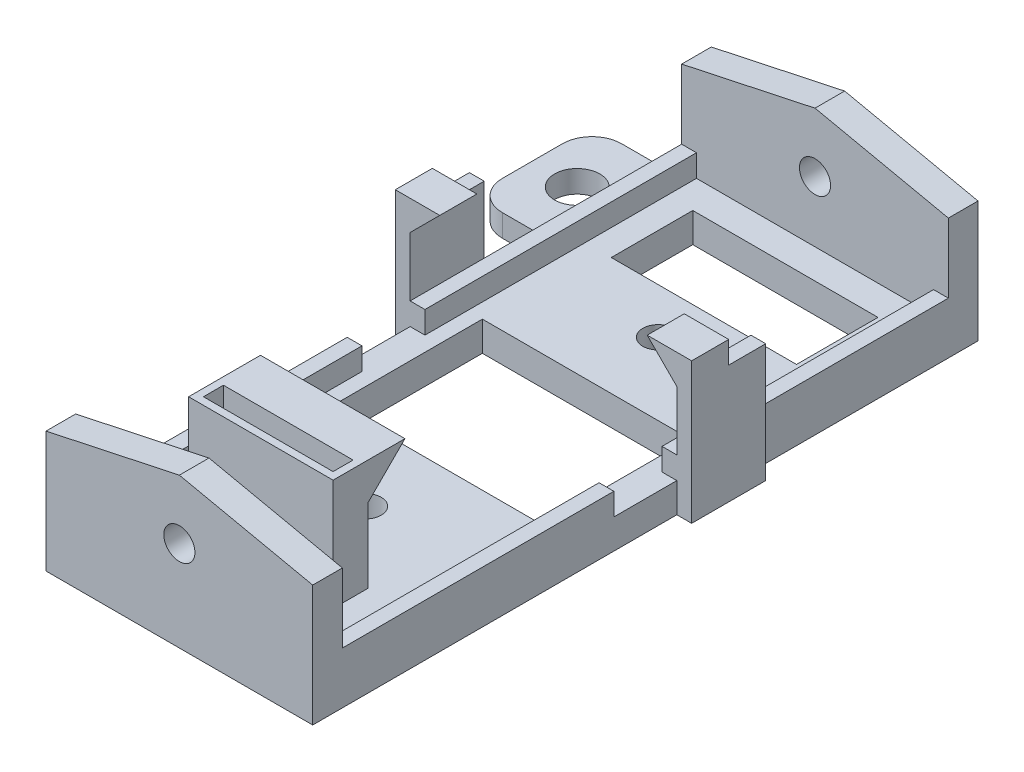
SolidWorks part; units mm, degrees
ref_plane "Front Plane" through (0, 0, 0) normal (0, 0, 1) x (1, 0, 0)
ref_plane "Top Plane" through (0, 0, 0) normal (0, 1, 0) x (1, 0, 0)
ref_plane "Right Plane" through (0, 0, 0) normal (1, 0, 0) x (0, 0, -1)
sketch "Sketch1" plane through (0, 0, 0) normal (0, 0, 1) x (1, 0, 0)
  line L2 (-40.4, 110) -> (0, 118.6383) construction
  line L3 (-18, 114.7896) -> (0, 114.7896)
  line L4 (0, 114.7896) -> (18, 114.7896)
  line L5 (0, 118.6383) -> (40.4, 110) construction
  line L11 (18, 114.7896) -> (18, 121.7896)
  line L12 (18, 121.7896) -> (16, 121.7896)
  line L13 (16, 121.7896) -> (16, 118.7896)
  line L14 (16, 118.7896) -> (-16, 118.7896)
  line L15 (-16, 118.7896) -> (-16, 121.7896)
  line L16 (-16, 121.7896) -> (-18, 121.7896)
  line L17 (-18, 121.7896) -> (-18, 114.7896)
  point P15 (0, 118.7896)
  dimension "D1" = 32
  dimension "D2" = 2
  dimension "D3" = 3
  dimension "D4" = 4
extrude "Boss-Extrude1" add sketch "Sketch1" along normal up to surface (89.8 mm away)
sketch "Sketch2" plane through (0, 114.7896, 0) normal (0, -1, 0) x (1, 0, 0)
  line L0 (18, 89.8) -> (18, 0) construction
  line L5 (-14, 54.9) -> (14, 54.9)
  line L6 (-14, 54.9) -> (-14, 34.9)
  line L7 (-14, 34.9) -> (14, 34.9)
  line L8 (14, 54.9) -> (14, 34.9)
  point P4 (0, 34.9)
  point P8 (18, 44.9)
  point P9 (14, 44.9)
  dimension "D1" = 4
  dimension "D2" = 20
extrude "Cut-Extrude1" cut sketch "Sketch2" against normal up to next
sketch "Sketch3" plane through (-18, 0, 0) normal (-1, 0, 0) x (0, 0, 1)
  line L0 (89.8, 121.7896) -> (0, 121.7896) construction
  line L1 (40.65, 118.7896) -> (49.15, 118.7896)
  line L2 (40.65, 118.7896) -> (40.65, 121.7896)
  line L3 (40.65, 121.7896) -> (49.15, 121.7896)
  line L4 (49.15, 118.7896) -> (49.15, 121.7896)
  line L5 (89.8, 118.7896) -> (0, 118.7896) construction
  point P9 (44.9, 121.7896)
  point P10 (44.9, 121.7896)
  dimension "D1" = 8.5
extrude "Cut-Extrude2" cut sketch "Sketch3" against normal through all
sketch "Sketch4" plane through (0, 118.7896, 0) normal (0, 1, 0) x (1, 0, 0)
  circle A0 centre (0, -25.15) radius 2.1 construction
  circle A1 centre (0, -64.65) radius 2.1 construction
  circle A2 centre (0, -25.15) radius 2.1
  circle A3 centre (0, -64.65) radius 2.1
extrude "Cut-Extrude3" cut sketch "Sketch4" against normal through all
ref_plane "Plane2" through (0, 0, 44.9) normal (0, 0, -1) x (-1, 0, 0)
sketch "Sketch5" plane through (0, 0, 0) normal (0, 0, 1) x (1, 0, 0)
  line L0 (-18, 114.7896) -> (-18, 131.1512)
  line L1 (-56.4, 122.9405) -> (0, 135) construction
  line L2 (-18, 131.1512) -> (0, 135)
  line L3 (0, 135) -> (18, 131.1512)
  line L4 (0, 135) -> (56.4, 122.9405) construction
  line L5 (18, 131.1512) -> (18, 114.7896)
  line L6 (18, 114.7896) -> (-18, 114.7896)
  line L7 (0.6273, 134.8659) -> (54.0273, 123.4479) construction
  line L8 (-54.0273, 123.4479) -> (-0.6273, 134.8659) construction
  circle A0 centre (0, 127) radius 2.1
  dimension "D1" = 4.2
  dimension "D2" = 8
extrude "Boss-Extrude2" add sketch "Sketch5" along normal blind 4
mirror "Mirror1" about plane through (0, 0, 44.9) normal (0, 0, -1) of "Boss-Extrude2"
sketch "Sketch6" plane through (0, 118.7896, 0) normal (0, 1, 0) x (1, 0, 0)
  line L1 (12.5, -19) -> (-12.5, -19)
  line L2 (12.5, -19) -> (12.5, -8)
  line L3 (12.5, -8) -> (-12.5, -8)
  line L4 (-12.5, -19) -> (-12.5, -8)
  point P4 (0, -8)
  dimension "D1" = 11
  dimension "D2" = 25
  dimension "D3" = 8
extrude "Cut-Extrude4" cut sketch "Sketch6" against normal through all
sketch "Sketch8" plane through (0, 118.7896, 0) normal (0, 1, 0) x (1, 0, 0)
  line L0 (16, -85.8) -> (-16, -85.8) construction
  line L1 (8.75, -77.8) -> (-8.75, -77.8)
  line L2 (8.75, -77.8) -> (8.75, -75.1)
  line L3 (8.75, -75.1) -> (-8.75, -75.1)
  line L4 (-8.75, -77.8) -> (-8.75, -75.1)
  line L6 (9.75, -74.1) -> (-9.75, -74.1)
  line L7 (-9.75, -78.8) -> (-9.75, -74.1)
  line L8 (9.75, -78.8) -> (-9.75, -78.8)
  line L9 (9.75, -78.8) -> (9.75, -74.1)
  point P6 (0, -85.8)
  point P7 (0, -77.8)
  dimension "D1" = 8
  dimension "D2" = 2.7
  dimension "D3" = 17.5
  dimension "D4" = 1
extrude "Boss-Extrude3" add sketch "Sketch8" along normal blind 15
sketch "Sketch9" plane through (-9.75, 0, 0) normal (-1, 0, 0) x (0, 0, 1)
  line L0 (74.1, 128.7896) -> (69.1, 133.7896)
  line L1 (74.1, 133.7896) -> (74.1, 118.7896) construction
  line L2 (69.1, 133.7896) -> (74.1, 133.7896)
  line L3 (74.1, 133.7896) -> (74.1, 128.7896)
  dimension "D1" = 5
  dimension "D2" = 45
extrude "Boss-Extrude4" add sketch "Sketch9" against normal up to surface (19.5 mm away) up to face at (9.75, 126.2896, 76.45)
sketch "Sketch13" plane through (0, 118.7896, 0) normal (0, 1, 0) x (1, 0, 0)
  line L4 (-8.75, -77.8) -> (8.75, -77.8)
  line L5 (8.75, -77.8) -> (8.75, -75.1)
  line L6 (8.75, -75.1) -> (-8.75, -75.1)
  line L7 (-8.75, -75.1) -> (-8.75, -77.8)
  line L8 (-8.75, -77.8) -> (8.75, -77.8)
  line L9 (8.75, -77.8) -> (8.75, -75.1)
  line L10 (8.75, -75.1) -> (-8.75, -75.1)
  line L11 (-8.75, -75.1) -> (-8.75, -77.8)
  dimension "D1" = 0
extrude "Cut-Extrude5" cut sketch "Sketch13" against normal through all
sketch "Sketch10" plane through (0, 114.7896, 0) normal (0, 1, 0) x (1, 0, 0)
  line L0 (18, -40.65) -> (18, -4) construction
  line L1 (18, -40.65) -> (20, -40.65)
  line L2 (18, -40.65) -> (18, -30.65)
  line L3 (18, -30.65) -> (20, -30.65)
  line L4 (20, -40.65) -> (20, -30.65)
  line L5 (0, -1000) -> (0, 49000) construction
  line L6 (-18, -30.65) -> (-20, -30.65)
  line L7 (-18, -40.65) -> (-18, -30.65)
  line L8 (-18, -40.65) -> (-20, -40.65)
  line L9 (-20, -40.65) -> (-20, -30.65)
  dimension "D1" = 10
  dimension "D2" = 2
extrude "Boss-Extrude5" add sketch "Sketch10" along normal offset from surface (16 mm away) 3
sketch "Sketch12" plane through (0, 0, 40.65) normal (0, 0, 1) x (1, 0, 0)
  line L0 (20, 129.7896) -> (20, 133.7896)
  line L1 (20, 133.7896) -> (14, 133.7896)
  line L2 (14, 133.7896) -> (18, 129.7896)
  line L3 (18, 129.7896) -> (20, 129.7896)
  line L4 (-18, 133.7896) -> (18, 133.7896) construction
  line L5 (18, 114.7896) -> (18, 131.1512) construction
  line L6 (20, 130.7896) -> (20, 114.7896) construction
  line L7 (18, 130.7896) -> (18, 121.7896) construction
  line L8 (0, -868.0678) -> (0, 49131.9322) construction
  line L9 (-18, 129.7896) -> (-20, 129.7896)
  line L10 (-14, 133.7896) -> (-18, 129.7896)
  line L11 (-20, 133.7896) -> (-14, 133.7896)
  line L12 (-20, 129.7896) -> (-20, 133.7896)
  dimension "D1" = 45
  dimension "D2" = 6
extrude "Boss-Extrude6" add sketch "Sketch12" against normal blind 5
sketch "Sketch14" plane through (0, 114.7896, 0) normal (0, 1, 0) x (1, 0, 0)
  line L0 (-18, -30.65) -> (-18, -4) construction
  line L1 (-18, -4) -> (-30.1, -4)
  line L2 (-18, -4) -> (-18, -20.1)
  line L3 (-18, -20.1) -> (-30.1, -20.1)
  line L4 (-30.1, -4) -> (-30.1, -20.1)
  circle A0 centre (-24.05, -12.05) radius 3.05
  point P9 (-30.1, -12.05)
  point P10 (-24.05, -20.1)
  dimension "D1" = 6.1
  dimension "D2" = 3
  dimension "D3" = 5
extrude "Boss-Extrude7" add sketch "Sketch14" along normal blind 3
fillet "Fillet1" radius 4 2 edges at (-30.1, 116.2896, 4) (-30.1, 116.2896, 20.1)
chamfer "Chamfer1" distance 3 angle 45 2 edges at (-18, 116.2896, 20.1) (-18, 116.2896, 4)
equation "\"width\"= 24"
equation "\"thk\"= 3"
equation "\"holesize\"= 4.2"
equation "\"holedistance\"= ( 20 + 12 ) / 2"
equation "\"threaded_hole\"= 3.9"
equation "\"fillet_radius\"= 2"
equation "\"ground_clearance\"= 25"
equation "\"tire_thk\"= 3"
equation "\"innerwheel_diam\" = \"wheel_diam\"-2*\"tire_thk\""
equation "\"innerwheel_thk\"= 8"
equation "\"wheel_diam\"= 2*(\"width\"/2+\"ground_clearance\")"
equation "\"coloursensor_holesize\"= 2.65"
equation "\"hole_to_edge\" = 4"
equation "\"D1@Sketch5\"=\"holesize\""
